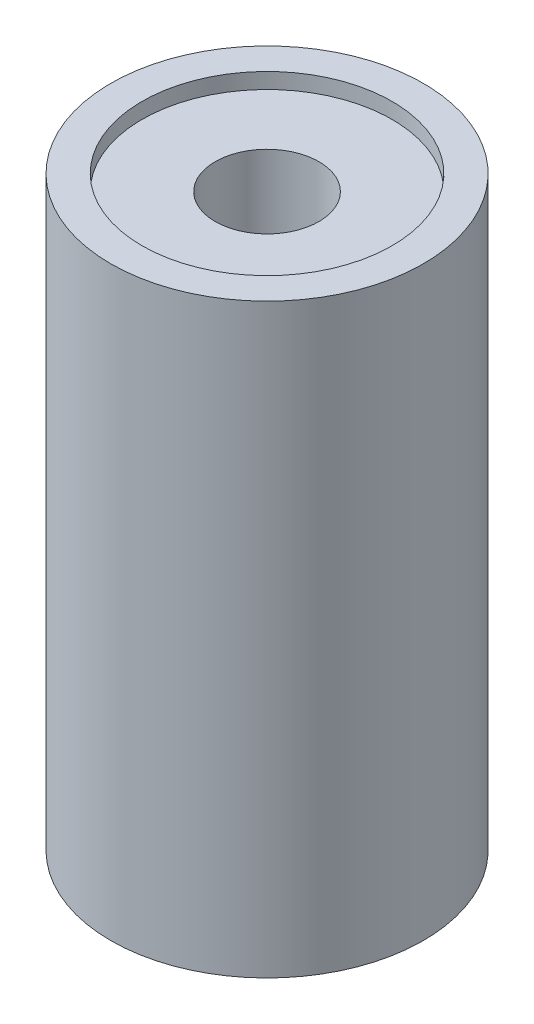
SolidWorks part; units mm, degrees
material "6061 Alloy"
ref_plane "Front Plane" through (0, 0, 0) normal (0, 0, 1) x (1, 0, 0)
ref_plane "Top Plane" through (0, 0, 0) normal (0, 1, 0) x (1, 0, 0)
ref_plane "Right Plane" through (0, 0, 0) normal (1, 0, 0) x (0, 0, -1)
sketch "Sketch1" plane through (0, 0, 0) normal (0, 1, 0) x (1, 0, 0)
  circle A0 centre (0, 0) radius 12.7
  dimension "D1" = 25.4
extrude "Boss-Extrude1" add sketch "Sketch1" along normal blind 23.8125 and the other way blind 23.8125
sketch "Sketch2" plane through (0, 23.8125, 0) normal (0, 1, 0) x (1, 0, 0)
  circle A0 centre (0, 0) radius 10.16
  dimension "D1" = 20.32
extrude "Cut-Extrude1" cut sketch "Sketch2" against normal blind 1.27
hole_wizard "3/8-24 Tapped Hole1" positions "Sketch3" profile "Sketch5" tap size "3/8-24" standard "ANSI Inch"
sketch "Sketch3" plane through (0, 22.5425, 0) normal (0, 1, 0) x (1, 0, 0)
  point P0 (0, 0)
sketch "Sketch5" plane through (0, 22.5425, 0) normal (1, 0, 0) x (0, 0, 1)
  line L0 (0, 0) -> (0, 18.5355)
  line L1 (0, 18.5355) -> (4.2164, 16.002)
  line L2 (4.2164, 16.002) -> (4.2164, 0)
  line L5 (4.2164, 0) -> (0, 0)
  line L10 (0, 18.5355) -> (-4.2164, 16.002) construction
  line L11 (0, -6.35) -> (0, 107.95) construction
  dimension "Tap Drill Dia." = 8.4328
  dimension "Tap Drill Depth" = 16.002
  dimension "Drill Angle" = 118
cosmetic thread "Hole Thread1" parameters "D1"=12.7, "D2"=9.525
mirror "Mirror1" about plane through (0, 0, 0) normal (0, 1, 0) of "3/8-24 Tapped Hole1", "Cut-Extrude1"
